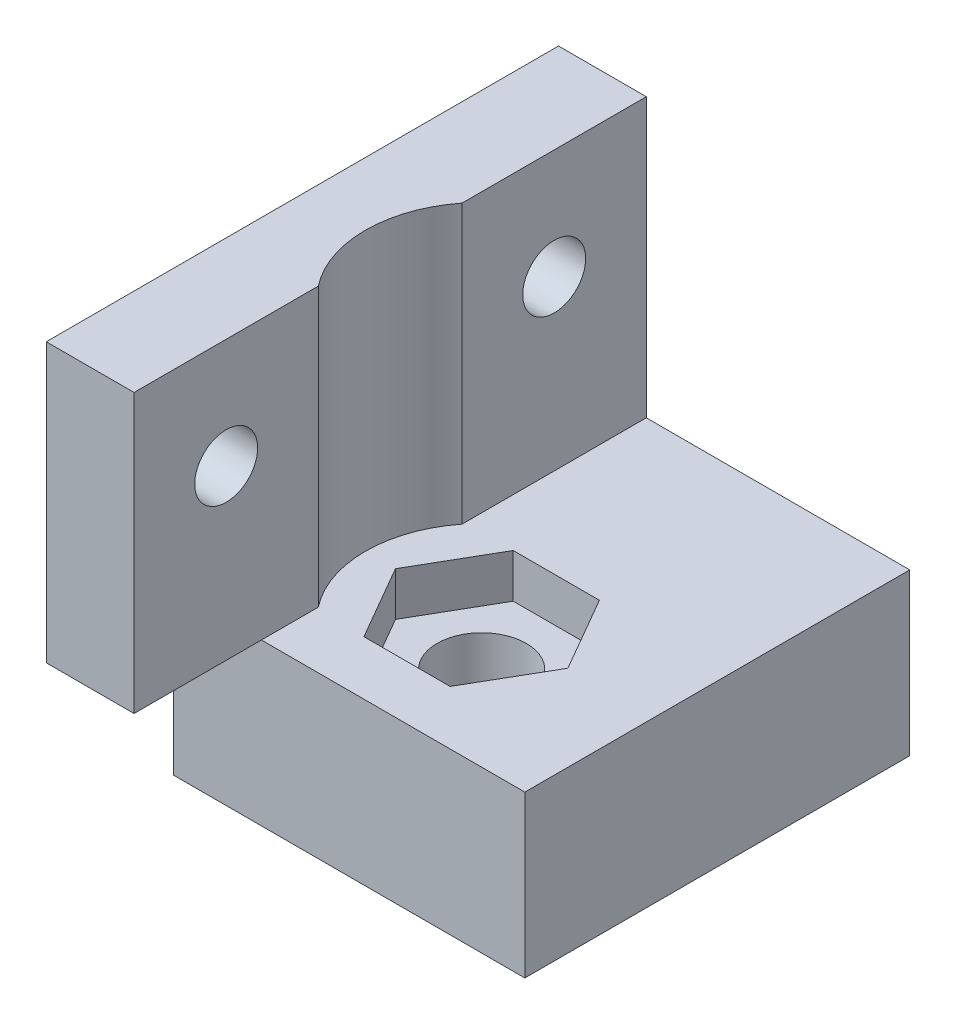
SolidWorks part; units mm, degrees
ref_plane "Front Plane" through (0, 0, 0) normal (0, 0, 1) x (1, 0, 0)
ref_plane "Top Plane" through (0, 0, 0) normal (0, 1, 0) x (1, 0, 0)
ref_plane "Right Plane" through (0, 0, 0) normal (1, 0, 0) x (0, 0, -1)
sketch "Sketch1" plane through (0, 0, 0) normal (0, 1, 0) x (1, 0, 0)
  line L1 (-3, 17.5) -> (3, 17.5)
  line L2 (-3, 17.5) -> (-3, -17.5)
  line L3 (-3, -17.5) -> (3, -17.5)
  line L4 (3, 17.5) -> (3, -17.5)
  line L5 (-3, 17.5) -> (3, -17.5) construction
  line L6 (-3, -17.5) -> (3, 17.5) construction
  line L7 (3, 17.5) -> (21, 17.5)
  line L8 (3, 17.5) -> (3, -17.5)
  line L9 (3, -17.5) -> (21, -17.5)
  line L10 (21, 17.5) -> (21, -17.5)
  circle A0 centre (9.25, 0) radius 3.05
  point P0 (0, 0)
  dimension "D1" = 6.1
  dimension "D2" = 12.25
  dimension "D3" = 6
  dimension "D4" = 24
  dimension "D5" = 35
  dimension "D6" = 17.5
extrude "Boss-Extrude1" add sketch "Sketch1" along normal blind 11 contours L10 L7 L4 L9 A0 region at (12, 0, -17.1064)
extrude "Boss-Extrude2" add sketch "Sketch1<3>" along normal blind 30 contours L4 L1 L2 L3 region at (0, 0, 0)
sketch "Sketch1<3>" plane through (0, 0, 0) normal (0, 1, 0) x (1, 0, 0) same geometry as "Sketch1"
sketch "Sketch2" plane through (0, 30, 0) normal (0, 1, 0) x (1, 0, 0)
  circle A0 centre (9.25, 0) radius 7.9493
extrude "Cut-Extrude1" cut sketch "Sketch2" against normal blind 19
sketch "Sketch4" plane through (0, 11, 0) normal (0, 1, 0) x (1, 0, 0)
  line L1 (15.139, 0) -> (12.1945, 5.1)
  line L2 (12.1945, 5.1) -> (6.3055, 5.1)
  line L3 (6.3055, 5.1) -> (3.361, 0)
  line L4 (3.361, 0) -> (6.3055, -5.1)
  line L5 (6.3055, -5.1) -> (12.1945, -5.1)
  line L6 (12.1945, -5.1) -> (15.139, 0)
  circle A0 centre (9.25, 0) radius 5.1 construction
  dimension "D1" = 10.2
extrude "Cut-Extrude3" cut sketch "Sketch4" against normal blind 3
sketch "Sketch5" plane through (0, 0, 0) normal (0, -1, 0) x (1, 0, 0)
  line L1 (3.361, 0) -> (6.3055, -5.1)
  line L2 (6.3055, -5.1) -> (12.1945, -5.1)
  line L3 (12.1945, -5.1) -> (15.139, 0)
  line L4 (15.139, 0) -> (12.1945, 5.1)
  line L5 (12.1945, 5.1) -> (6.3055, 5.1)
  line L6 (6.3055, 5.1) -> (3.361, 0)
  circle A0 centre (9.25, 0) radius 5.889 construction
  dimension "D1" = 10.2
extrude "Cut-Extrude4" cut sketch "Sketch5" against normal blind 3
sketch "Sketch7" plane through (3, 0, 0) normal (1, 0, 0) x (0, 0, -1)
  line L0 (-4.9121, 30) -> (-17.5, 30) construction
  line L3 (17.5, 30) -> (4.9121, 30) construction
  circle A0 centre (-11.206, 22.5) radius 2.15
  circle A1 centre (11.206, 22.5) radius 2.15
  dimension "D1" = 4.3
  dimension "D2" = 4.3
  dimension "D3" = 7.5
  dimension "D4" = 7.5
extrude "Cut-Extrude6" cut sketch "Sketch7" against normal blind 10
sketch "Sketch8" plane through (0, 0, 0) normal (0, -1, 0) x (1, 0, 0)
  line L0 (21, -17.5) -> (21, 17.5) construction
  line L1 (-3, 17.5) -> (21, 17.5)
  line L2 (-3, 17.5) -> (-3, 8.7994)
  line L3 (-3, 8.7994) -> (21, 8.7994)
  line L4 (21, 17.5) -> (21, 8.7994)
extrude "Cut-Extrude7" cut sketch "Sketch8" against normal blind 11
